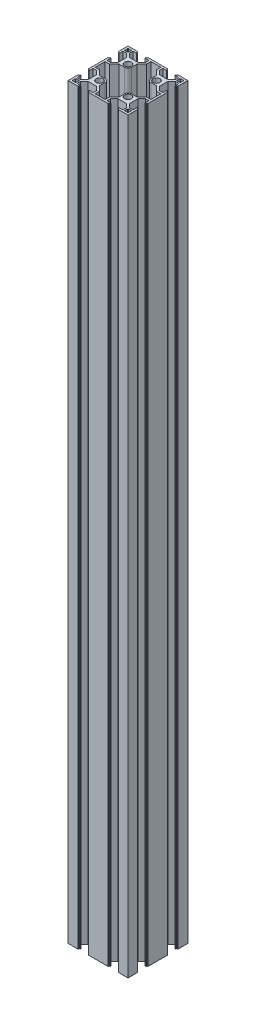
SolidWorks part; units mm, degrees
ref_plane "Front Plane" through (0, 0, 0) normal (0, 0, 1) x (1, 0, 0)
ref_plane "Top Plane" through (0, 0, 0) normal (0, 1, 0) x (1, 0, 0)
ref_plane "Right Plane" through (0, 0, 0) normal (1, 0, 0) x (0, 0, -1)
sketch "Sketch1" plane through (0, 0, 0) normal (0, 1, 0) x (1, 0, 0)
  line L0 (0, 30) -> (0, -30) construction
  line L1 (-30, -30) -> (30, -30)
  line L2 (-30, -30) -> (-30, 30)
  line L3 (-30, 30) -> (30, 30)
  line L4 (30, -30) -> (30, 30)
  line L5 (-30, -30) -> (30, 30) construction
  line L6 (-30, 30) -> (30, -30) construction
  line L7 (-30, 0) -> (30, 0) construction
  line L8 (-23.05, -28) -> (-6.95, -28)
  line L9 (-6.95, -28) -> (-6.95, -24.4)
  line L10 (-6.95, -24.4) -> (-10.615, -20.8)
  line L11 (-10.615, -20.8) -> (-19.385, -20.8)
  line L12 (-19.385, -20.8) -> (-23.05, -24.4)
  line L13 (-23.05, -24.4) -> (-23.05, -28)
  line L14 (10.615, -20.8) -> (19.385, -20.8)
  line L15 (6.95, -24.4) -> (10.615, -20.8)
  line L16 (6.95, -28) -> (6.95, -24.4)
  line L17 (23.05, -28) -> (6.95, -28)
  line L18 (23.05, -24.4) -> (23.05, -28)
  line L19 (19.385, -20.8) -> (23.05, -24.4)
  line L20 (19.385, 20.8) -> (23.05, 24.4)
  line L21 (23.05, 24.4) -> (23.05, 28)
  line L22 (23.05, 28) -> (6.95, 28)
  line L23 (6.95, 28) -> (6.95, 24.4)
  line L24 (6.95, 24.4) -> (10.615, 20.8)
  line L25 (10.615, 20.8) -> (19.385, 20.8)
  line L26 (-23.05, 24.4) -> (-23.05, 28)
  line L27 (-19.385, 20.8) -> (-23.05, 24.4)
  line L28 (-10.615, 20.8) -> (-19.385, 20.8)
  line L29 (-6.95, 24.4) -> (-10.615, 20.8)
  line L30 (-6.95, 28) -> (-6.95, 24.4)
  line L31 (-23.05, 28) -> (-6.95, 28)
  line L32 (-20.8, 19.385) -> (-24.4, 23.05)
  line L33 (-24.4, 23.05) -> (-28, 23.05)
  line L34 (-28, 23.05) -> (-28, 6.95)
  line L35 (-28, 6.95) -> (-24.4, 6.95)
  line L36 (-24.4, 6.95) -> (-20.8, 10.615)
  line L37 (-20.8, 10.615) -> (-20.8, 19.385)
  line L38 (-24.4, -23.05) -> (-28, -23.05)
  line L39 (-20.8, -19.385) -> (-24.4, -23.05)
  line L40 (-20.8, -10.615) -> (-20.8, -19.385)
  line L41 (-24.4, -6.95) -> (-20.8, -10.615)
  line L42 (-28, -6.95) -> (-24.4, -6.95)
  line L43 (-28, -23.05) -> (-28, -6.95)
  line L44 (20.8, -19.385) -> (24.4, -23.05)
  line L45 (24.4, -23.05) -> (28, -23.05)
  line L46 (28, -23.05) -> (28, -6.95)
  line L47 (28, -6.95) -> (24.4, -6.95)
  line L48 (24.4, -6.95) -> (20.8, -10.615)
  line L49 (20.8, -10.615) -> (20.8, -19.385)
  line L50 (24.4, 23.05) -> (28, 23.05)
  line L51 (20.8, 19.385) -> (24.4, 23.05)
  line L52 (20.8, 10.615) -> (20.8, 19.385)
  line L53 (24.4, 6.95) -> (20.8, 10.615)
  line L54 (28, 6.95) -> (24.4, 6.95)
  line L55 (28, 23.05) -> (28, 6.95)
  point P0 (0, 0)
  dimension "D1" = 60
  dimension "D2" = 16.1
  dimension "D3" = 8.77
  dimension "D4" = 3.6
  dimension "D5" = 7.2
  dimension "D6" = 2
  dimension "D7" = 6.95
extrude "Boss-Extrude1" add sketch "Sketch1" along normal blind 750
sketch "Sketch2" plane through (0, 750, 0) normal (0, 1, 0) x (1, 0, 0)
  line L0 (-19.1, -28) -> (-19.1, -29)
  line L1 (-23.05, -28) -> (-6.95, -28) construction
  line L2 (-30, -30) -> (30, -30) construction
  line L3 (-10.9, -28) -> (-10.9, -29)
  line L4 (-10.9, -29) -> (-9.9, -29)
  line L5 (-9.9, -29) -> (-9.9, -30)
  line L6 (-19.1, -29) -> (-20.1, -29)
  line L7 (-20.1, -29) -> (-20.1, -30)
  line L8 (-19.1, -28) -> (-10.9, -28)
  line L9 (-20.1, -30) -> (-9.9, -30)
  dimension "D1" = 8.2
  dimension "D2" = 3.95
  dimension "D3" = 1
  dimension "D4" = 1
extrude "Cut-Extrude1" cut sketch "Sketch2" against normal through all
mirror "Mirror1" about plane through (0, 0, 0) normal (1, 0, 0) of "Cut-Extrude1"
ref_axis "Axis1" through (0, 1050, 0) along (0, -1, 0)
pattern_circular "CirPattern1" count 4 over 360 about axis through (0, 1050, 0) along (0, -1, 0) of "Cut-Extrude1", "Mirror1"
sketch "Sketch4" plane through (0, 750, 0) normal (0, 1, 0) x (1, 0, 0)
  line L0 (19.385, 18.8) -> (9.797, 18.8) construction
  line L1 (-18.8, 18.8) -> (-18.8, 9.797)
  line L2 (18.8, -19.385) -> (18.8, -9.797) construction
  line L3 (28, 4.95) -> (28, -4.95)
  line L4 (-18.8, -9.797) -> (-18.8, -19.385) construction
  line L5 (4.95, -28) -> (-4.95, -28)
  line L6 (-9.797, 18.8) -> (-9.797, 13.197)
  line L7 (-28, -4.95) -> (-28, 4.95)
  line L8 (-18.8, 9.797) -> (-23.5611, 4.95)
  line L9 (-23.5611, 4.95) -> (-28, 4.95)
  line L10 (18.8, 18.8) -> (9.797, 18.8)
  line L11 (9.797, 18.8) -> (4.95, 23.5611)
  line L12 (4.95, 23.5611) -> (4.95, 28)
  line L13 (4.95, 28) -> (4.95, 28)
  line L14 (4.95, 28) -> (4.95, 28)
  line L15 (4.95, 28) -> (4.95, 28)
  line L16 (4.95, 28) -> (4.95, 28)
  line L17 (4.95, 28) -> (-4.95, 28)
  line L18 (-4.95, 28) -> (-4.95, 28)
  line L19 (-4.95, 28) -> (-4.95, 28)
  line L20 (-4.95, 28) -> (-4.95, 28)
  line L21 (-4.95, 28) -> (-4.95, 28)
  line L22 (-4.95, 28) -> (-4.95, 23.5611)
  line L23 (-4.95, 23.5611) -> (-9.797, 18.8)
  line L24 (-9.797, 18.8) -> (-18.8, 18.8)
  line L25 (28, 4.95) -> (23.5611, 4.95)
  line L26 (23.5611, 4.95) -> (18.8, 9.797)
  line L27 (18.8, 9.797) -> (18.8, 18.8)
  line L28 (18.8, -18.8) -> (18.8, -9.797)
  line L29 (18.8, -9.797) -> (23.5611, -4.95)
  line L30 (23.5611, -4.95) -> (28, -4.95)
  line L31 (4.95, -28) -> (4.95, -23.5611)
  line L32 (4.95, -23.5611) -> (9.797, -18.8)
  line L33 (9.797, -18.8) -> (18.8, -18.8)
  line L34 (-18.8, -18.8) -> (-9.797, -18.8)
  line L35 (-9.797, -18.8) -> (-4.95, -23.5611)
  line L36 (-4.95, -23.5611) -> (-4.95, -28)
  line L37 (-28, -4.95) -> (-23.5611, -4.95)
  line L38 (-23.5611, -4.95) -> (-18.8, -9.797)
  line L39 (-18.8, -9.797) -> (-18.8, -18.8)
  line L40 (-9.797, 18.8) -> (-19.385, 18.8) construction
  line L41 (-18.8, 19.385) -> (-18.8, 9.797) construction
  line L42 (18.8, 9.797) -> (18.8, 19.385) construction
  line L43 (9.797, -18.8) -> (19.385, -18.8) construction
  line L44 (-19.385, -18.8) -> (-9.797, -18.8) construction
  line L45 (-13.197, 9.797) -> (-18.8, 9.797)
  line L46 (9.797, 18.8) -> (9.797, 13.197)
  line L47 (13.197, 9.797) -> (18.8, 9.797)
  line L48 (-18.8, -9.797) -> (-13.197, -9.797)
  line L49 (-9.797, -13.197) -> (-9.797, -18.8)
  line L50 (9.797, -18.8) -> (9.797, -13.197)
  line L51 (13.197, -9.797) -> (18.8, -9.797)
  line L52 (-27.5, -28) -> (-24.9, -28)
  line L53 (24.9, -28) -> (27.5, -28)
  line L54 (24.4, -27.5) -> (24.4, -24.9)
  line L55 (24.9, -24.4) -> (27.5, -24.4)
  line L56 (28, -27.5) -> (28, -24.9)
  line L57 (24.4, -28) -> (28, -24.4) construction
  line L58 (24.4, -24.4) -> (28, -28) construction
  line L59 (-28, -24.9) -> (-28, -27.5)
  line L60 (-27.5, -24.4) -> (-24.9, -24.4)
  line L61 (-24.4, -24.9) -> (-24.4, -27.5)
  line L62 (-28, 27.5) -> (-28, 24.9)
  line L63 (-24.9, 28) -> (-27.5, 28)
  line L64 (-24.4, 27.5) -> (-24.4, 24.9)
  line L65 (-24.9, 24.4) -> (-27.5, 24.4)
  line L66 (27.5, 28) -> (24.9, 28)
  line L67 (28, 24.9) -> (28, 27.5)
  line L68 (27.5, 24.4) -> (24.9, 24.4)
  line L69 (24.4, 24.9) -> (24.4, 27.5)
  line L116 (28, 19.1) -> (29, 19.1)
  line L117 (29, 19.1) -> (29, 20.1)
  line L118 (29, 20.1) -> (30, 20.1)
  line L119 (30, 20.1) -> (30, 30)
  line L120 (30, 30) -> (20.1, 30)
  line L121 (20.1, 30) -> (20.1, 29)
  line L122 (20.1, 29) -> (19.1, 29)
  line L123 (19.1, 29) -> (19.1, 28)
  line L124 (19.1, 28) -> (23.05, 28)
  line L125 (23.05, 28) -> (23.05, 24.4)
  line L126 (23.05, 24.4) -> (19.385, 20.8)
  line L127 (19.385, 20.8) -> (10.615, 20.8)
  line L128 (10.615, 20.8) -> (6.95, 24.4)
  line L129 (6.95, 24.4) -> (6.95, 28)
  line L130 (6.95, 28) -> (10.9, 28)
  line L131 (10.9, 28) -> (10.9, 29)
  line L132 (10.9, 29) -> (9.9, 29)
  line L133 (9.9, 29) -> (9.9, 30)
  line L134 (9.9, 30) -> (-9.9, 30)
  line L135 (-9.9, 30) -> (-9.9, 29)
  line L136 (-9.9, 29) -> (-10.9, 29)
  line L137 (-10.9, 29) -> (-10.9, 28)
  line L138 (-10.9, 28) -> (-6.95, 28)
  line L139 (-6.95, 28) -> (-6.95, 24.4)
  line L140 (-6.95, 24.4) -> (-10.615, 20.8)
  line L141 (-10.615, 20.8) -> (-19.385, 20.8)
  line L142 (-19.385, 20.8) -> (-23.05, 24.4)
  line L143 (-23.05, 24.4) -> (-23.05, 28)
  line L144 (-23.05, 28) -> (-19.1, 28)
  line L145 (-19.1, 28) -> (-19.1, 29)
  line L146 (-19.1, 29) -> (-20.1, 29)
  line L147 (-20.1, 29) -> (-20.1, 30)
  line L148 (-20.1, 30) -> (-30, 30)
  line L149 (-30, 30) -> (-30, 20.1)
  line L150 (-30, 20.1) -> (-29, 20.1)
  line L151 (-29, 20.1) -> (-29, 19.1)
  line L152 (-29, 19.1) -> (-28, 19.1)
  line L153 (-28, 19.1) -> (-28, 23.05)
  line L154 (-28, 23.05) -> (-24.4, 23.05)
  line L155 (-24.4, 23.05) -> (-20.8, 19.385)
  line L156 (-20.8, 19.385) -> (-20.8, 10.615)
  line L157 (-20.8, 10.615) -> (-24.4, 6.95)
  line L158 (-24.4, 6.95) -> (-28, 6.95)
  line L159 (-28, 6.95) -> (-28, 10.9)
  line L160 (-28, 10.9) -> (-29, 10.9)
  line L161 (-29, 10.9) -> (-29, 9.9)
  line L162 (-29, 9.9) -> (-30, 9.9)
  line L163 (-30, 9.9) -> (-30, -9.9)
  line L164 (-30, -9.9) -> (-29, -9.9)
  line L165 (-29, -9.9) -> (-29, -10.9)
  line L166 (-29, -10.9) -> (-28, -10.9)
  line L167 (-28, -10.9) -> (-28, -6.95)
  line L168 (-28, -6.95) -> (-24.4, -6.95)
  line L169 (-24.4, -6.95) -> (-20.8, -10.615)
  line L170 (-20.8, -10.615) -> (-20.8, -19.385)
  line L171 (-20.8, -19.385) -> (-24.4, -23.05)
  line L172 (-24.4, -23.05) -> (-28, -23.05)
  line L173 (-28, -23.05) -> (-28, -19.1)
  line L174 (-28, -19.1) -> (-29, -19.1)
  line L175 (-29, -19.1) -> (-29, -20.1)
  line L176 (-29, -20.1) -> (-30, -20.1)
  line L177 (-30, -20.1) -> (-30, -30)
  line L178 (-30, -30) -> (-20.1, -30)
  line L179 (-20.1, -30) -> (-20.1, -29)
  line L180 (-20.1, -29) -> (-19.1, -29)
  line L181 (-19.1, -29) -> (-19.1, -28)
  line L182 (-19.1, -28) -> (-23.05, -28)
  line L183 (-23.05, -28) -> (-23.05, -24.4)
  line L184 (-23.05, -24.4) -> (-19.385, -20.8)
  line L185 (-19.385, -20.8) -> (-10.615, -20.8)
  line L186 (-10.615, -20.8) -> (-6.95, -24.4)
  line L187 (-6.95, -24.4) -> (-6.95, -28)
  line L188 (-6.95, -28) -> (-10.9, -28)
  line L189 (-10.9, -28) -> (-10.9, -29)
  line L190 (-10.9, -29) -> (-9.9, -29)
  line L191 (-9.9, -29) -> (-9.9, -30)
  line L192 (-9.9, -30) -> (9.9, -30)
  line L193 (9.9, -30) -> (9.9, -29)
  line L194 (9.9, -29) -> (10.9, -29)
  line L195 (10.9, -29) -> (10.9, -28)
  line L196 (10.9, -28) -> (6.95, -28)
  line L197 (6.95, -28) -> (6.95, -24.4)
  line L198 (6.95, -24.4) -> (10.615, -20.8)
  line L199 (10.615, -20.8) -> (19.385, -20.8)
  line L200 (19.385, -20.8) -> (23.05, -24.4)
  line L201 (23.05, -24.4) -> (23.05, -28)
  line L202 (23.05, -28) -> (19.1, -28)
  line L203 (19.1, -28) -> (19.1, -29)
  line L204 (19.1, -29) -> (20.1, -29)
  line L205 (20.1, -29) -> (20.1, -30)
  line L206 (20.1, -30) -> (30, -30)
  line L207 (30, -30) -> (30, -20.1)
  line L208 (30, -20.1) -> (29, -20.1)
  line L209 (29, -20.1) -> (29, -19.1)
  line L210 (29, -19.1) -> (28, -19.1)
  line L211 (28, -19.1) -> (28, -23.05)
  line L212 (28, -23.05) -> (24.4, -23.05)
  line L213 (24.4, -23.05) -> (20.8, -19.385)
  line L214 (20.8, -19.385) -> (20.8, -10.615)
  line L215 (20.8, -10.615) -> (24.4, -6.95)
  line L216 (24.4, -6.95) -> (28, -6.95)
  line L217 (28, -6.95) -> (28, -10.9)
  line L218 (28, -10.9) -> (29, -10.9)
  line L219 (29, -10.9) -> (29, -9.9)
  line L220 (29, -9.9) -> (30, -9.9)
  line L221 (30, -9.9) -> (30, 9.9)
  line L222 (30, 9.9) -> (29, 9.9)
  line L223 (29, 9.9) -> (29, 10.9)
  line L224 (29, 10.9) -> (28, 10.9)
  line L225 (28, 10.9) -> (28, 6.95)
  line L226 (28, 6.95) -> (24.4, 6.95)
  line L227 (24.4, 6.95) -> (20.8, 10.615)
  line L228 (20.8, 10.615) -> (20.8, 19.385)
  line L229 (20.8, 19.385) -> (24.4, 23.05)
  line L230 (24.4, 23.05) -> (28, 23.05)
  line L231 (28, 23.05) -> (28, 19.1)
  line L232 (28, 19.1) -> (29, 19.1)
  line L233 (29, 19.1) -> (29, 20.1)
  line L234 (29, 20.1) -> (30, 20.1)
  line L235 (30, 20.1) -> (30, 30)
  line L236 (30, 30) -> (20.1, 30)
  line L237 (20.1, 30) -> (20.1, 29)
  line L238 (20.1, 29) -> (19.1, 29)
  line L239 (19.1, 29) -> (19.1, 28)
  line L240 (19.1, 28) -> (23.05, 28)
  line L241 (23.05, 28) -> (23.05, 24.4)
  line L242 (23.05, 24.4) -> (19.385, 20.8)
  line L243 (19.385, 20.8) -> (10.615, 20.8)
  line L244 (10.615, 20.8) -> (6.95, 24.4)
  line L245 (6.95, 24.4) -> (6.95, 28)
  line L246 (6.95, 28) -> (10.9, 28)
  line L247 (10.9, 28) -> (10.9, 29)
  line L248 (10.9, 29) -> (9.9, 29)
  line L249 (9.9, 29) -> (9.9, 30)
  line L250 (9.9, 30) -> (-9.9, 30)
  line L251 (-9.9, 30) -> (-9.9, 29)
  line L252 (-9.9, 29) -> (-10.9, 29)
  line L253 (-10.9, 29) -> (-10.9, 28)
  line L254 (-10.9, 28) -> (-6.95, 28)
  line L255 (-6.95, 28) -> (-6.95, 24.4)
  line L256 (-6.95, 24.4) -> (-10.615, 20.8)
  line L257 (-10.615, 20.8) -> (-19.385, 20.8)
  line L258 (-19.385, 20.8) -> (-23.05, 24.4)
  line L259 (-23.05, 24.4) -> (-23.05, 28)
  line L260 (-23.05, 28) -> (-19.1, 28)
  line L261 (-19.1, 28) -> (-19.1, 29)
  line L262 (-19.1, 29) -> (-20.1, 29)
  line L263 (-20.1, 29) -> (-20.1, 30)
  line L264 (-20.1, 30) -> (-30, 30)
  line L265 (-30, 30) -> (-30, 20.1)
  line L266 (-30, 20.1) -> (-29, 20.1)
  line L267 (-29, 20.1) -> (-29, 19.1)
  line L268 (-29, 19.1) -> (-28, 19.1)
  line L269 (-28, 19.1) -> (-28, 23.05)
  line L270 (-28, 23.05) -> (-24.4, 23.05)
  line L271 (-24.4, 23.05) -> (-20.8, 19.385)
  line L272 (-20.8, 19.385) -> (-20.8, 10.615)
  line L273 (-20.8, 10.615) -> (-24.4, 6.95)
  line L274 (-24.4, 6.95) -> (-28, 6.95)
  line L275 (-28, 6.95) -> (-28, 10.9)
  line L276 (-28, 10.9) -> (-29, 10.9)
  line L277 (-29, 10.9) -> (-29, 9.9)
  line L278 (-29, 9.9) -> (-30, 9.9)
  line L279 (-30, 9.9) -> (-30, -9.9)
  line L280 (-30, -9.9) -> (-29, -9.9)
  line L281 (-29, -9.9) -> (-29, -10.9)
  line L282 (-29, -10.9) -> (-28, -10.9)
  line L283 (-28, -10.9) -> (-28, -6.95)
  line L284 (-28, -6.95) -> (-24.4, -6.95)
  line L285 (-24.4, -6.95) -> (-20.8, -10.615)
  line L286 (-20.8, -10.615) -> (-20.8, -19.385)
  line L287 (-20.8, -19.385) -> (-24.4, -23.05)
  line L288 (-24.4, -23.05) -> (-28, -23.05)
  line L289 (-28, -23.05) -> (-28, -19.1)
  line L290 (-28, -19.1) -> (-29, -19.1)
  line L291 (-29, -19.1) -> (-29, -20.1)
  line L292 (-29, -20.1) -> (-30, -20.1)
  line L293 (-30, -20.1) -> (-30, -30)
  line L294 (-30, -30) -> (-20.1, -30)
  line L295 (-20.1, -30) -> (-20.1, -29)
  line L296 (-20.1, -29) -> (-19.1, -29)
  line L297 (-19.1, -29) -> (-19.1, -28)
  line L298 (-19.1, -28) -> (-23.05, -28)
  line L299 (-23.05, -28) -> (-23.05, -24.4)
  line L300 (-23.05, -24.4) -> (-19.385, -20.8)
  line L301 (-19.385, -20.8) -> (-10.615, -20.8)
  line L302 (-10.615, -20.8) -> (-6.95, -24.4)
  line L303 (-6.95, -24.4) -> (-6.95, -28)
  line L304 (-6.95, -28) -> (-10.9, -28)
  line L305 (-10.9, -28) -> (-10.9, -29)
  line L306 (-10.9, -29) -> (-9.9, -29)
  line L307 (-9.9, -29) -> (-9.9, -30)
  line L308 (-9.9, -30) -> (9.9, -30)
  line L309 (9.9, -30) -> (9.9, -29)
  line L310 (9.9, -29) -> (10.9, -29)
  line L311 (10.9, -29) -> (10.9, -28)
  line L312 (10.9, -28) -> (6.95, -28)
  line L313 (6.95, -28) -> (6.95, -24.4)
  line L314 (6.95, -24.4) -> (10.615, -20.8)
  line L315 (10.615, -20.8) -> (19.385, -20.8)
  line L316 (19.385, -20.8) -> (23.05, -24.4)
  line L317 (23.05, -24.4) -> (23.05, -28)
  line L318 (23.05, -28) -> (19.1, -28)
  line L319 (19.1, -28) -> (19.1, -29)
  line L320 (19.1, -29) -> (20.1, -29)
  line L321 (20.1, -29) -> (20.1, -30)
  line L322 (20.1, -30) -> (30, -30)
  line L323 (30, -30) -> (30, -20.1)
  line L324 (30, -20.1) -> (29, -20.1)
  line L325 (29, -20.1) -> (29, -19.1)
  line L326 (29, -19.1) -> (28, -19.1)
  line L327 (28, -19.1) -> (28, -23.05)
  line L328 (28, -23.05) -> (24.4, -23.05)
  line L329 (24.4, -23.05) -> (20.8, -19.385)
  line L330 (20.8, -19.385) -> (20.8, -10.615)
  line L331 (20.8, -10.615) -> (24.4, -6.95)
  line L332 (24.4, -6.95) -> (28, -6.95)
  line L333 (28, -6.95) -> (28, -10.9)
  line L334 (28, -10.9) -> (29, -10.9)
  line L335 (29, -10.9) -> (29, -9.9)
  line L336 (29, -9.9) -> (30, -9.9)
  line L337 (30, -9.9) -> (30, 9.9)
  line L338 (30, 9.9) -> (29, 9.9)
  line L339 (29, 9.9) -> (29, 10.9)
  line L340 (29, 10.9) -> (28, 10.9)
  line L341 (28, 10.9) -> (28, 6.95)
  line L342 (28, 6.95) -> (24.4, 6.95)
  line L343 (24.4, 6.95) -> (20.8, 10.615)
  line L344 (20.8, 10.615) -> (20.8, 19.385)
  line L345 (20.8, 19.385) -> (24.4, 23.05)
  line L346 (24.4, 23.05) -> (28, 23.05)
  line L347 (28, 23.05) -> (28, 19.1)
  circle A0 centre (14.2985, 14.2985) radius 3.4
  arc A1 (13.197, -9.797) -> (9.797, -13.197) centre (13.197, -13.197) ccw
  arc A2 (-9.797, -13.197) -> (-13.197, -9.797) centre (-13.197, -13.197) ccw
  arc A3 (13.197, 9.797) -> (9.797, 13.197) centre (13.197, 13.197) cw
  arc A4 (-9.797, 13.197) -> (-13.197, 9.797) centre (-13.197, 13.197) cw
  circle A5 centre (14.2985, -14.2985) radius 3.4
  circle A6 centre (-14.2985, -14.2985) radius 3.4
  circle A7 centre (-14.2985, 14.2985) radius 3.4
  arc A8 (24.4, -27.5) -> (24.9, -28) centre (24.9, -27.5) ccw
  arc A9 (28, -27.5) -> (27.5, -28) centre (27.5, -27.5) cw
  arc A10 (28, -24.9) -> (27.5, -24.4) centre (27.5, -24.9) ccw
  arc A11 (24.4, -24.9) -> (24.9, -24.4) centre (24.9, -24.9) cw
  arc A12 (-27.5, -28) -> (-28, -27.5) centre (-27.5, -27.5) cw
  arc A13 (-27.5, -24.4) -> (-28, -24.9) centre (-27.5, -24.9) ccw
  arc A14 (-24.9, -24.4) -> (-24.4, -24.9) centre (-24.9, -24.9) cw
  arc A15 (-24.9, -28) -> (-24.4, -27.5) centre (-24.9, -27.5) ccw
  arc A16 (-28, 27.5) -> (-27.5, 28) centre (-27.5, 27.5) cw
  arc A17 (-24.4, 27.5) -> (-24.9, 28) centre (-24.9, 27.5) ccw
  arc A18 (-24.4, 24.9) -> (-24.9, 24.4) centre (-24.9, 24.9) cw
  arc A19 (-28, 24.9) -> (-27.5, 24.4) centre (-27.5, 24.9) ccw
  arc A20 (27.5, 28) -> (28, 27.5) centre (27.5, 27.5) cw
  arc A21 (27.5, 24.4) -> (28, 24.9) centre (27.5, 24.9) ccw
  arc A22 (24.9, 24.4) -> (24.4, 24.9) centre (24.9, 24.9) cw
  arc A23 (24.9, 28) -> (24.4, 27.5) centre (24.9, 27.5) ccw
  point P102 (26.2, -26.2)
  point P104 (14.2985, 18.8)
  point P106 (18.8, 14.2985)
  point P140 (0, 0)
  point P239 (0, 0)
  dimension "D3" = 6.8
  dimension "D4" = 3.4
  dimension "D6" = 0.5
  dimension "D1" = 0
  dimension "D2" = 2
  dimension "D5" = 4
  dimension "D7" = 4
extrude "Cut-Extrude2" cut sketch "Sketch4" against normal through all contours L6 A4 L45 L8 L9 L7 L37 L38 L48 A2 L49 L35 L36 L5 L31 L32 L50 A1 L51 L29 L30 L3 L25 L26 L47 A3 L46 L11 L12 L17 L22 L23 | A7 | A0 | L66 A23 L69 A22 L68 A21 L67 A20 | L62 A19 L65 A18 L64 A17 L63 A16 | L52 A15 L61 A14 L60 A13 L59 A12 | A11 L54 A8 L53 A9 L56 A10 L55 | A6 | A5 region at (0, 750, 0) region at (-26.2, 750, 26.2) region at (26.2, 750, 26.2) region at (-26.2, 750, -26.2) region at (26.2, 750, -26.2) region at (14.2985, 750, -14.2985) region at (-14.2985, 750, -14.2985)
fillet "Fillet1" radius 0.2 16 edges at (28, 375, -19.1) (30, 375, -20.1) (29, 375, -20.1) (29, 375, -19.1) (28, 375, 10.9) (29, 375, 9.9) (28, 375, 19.1) (29, 375, 20.1) (30, 375, 20.1) (29, 375, 19.1) (29, 375, 10.9) (30, 375, 9.9) (30, 375, -9.9) (29, 375, -9.9) (29, 375, -10.9) (28, 375, -10.9)
fillet "Fillet2" radius 0.2 20 edges at (-20.1, 0, -29.5) (-20.1, 750, -29.5) (-20.1, 375, -29) (-19.6, 0, -29) (-19.1, 375, -29) (-19.6, 750, -29) (-9.9, 375, -30) (-10.9, 375, -28) (-10.9, 375, -29) (-9.9, 375, -29) (19.1, 375, -28) (19.1, 375, -29) (20.1, 375, -29) (20.1, 375, -30) (10.9, 375, -28) (10.9, 375, -29) (9.9, 375, -29) (9.9, 375, -30) (-19.1, 375, -28) (-20.1, 375, -30)
fillet "Fillet3" radius 0.2 14 edges at (-29, 375, 9.9) (-29, 375, -20.1) (-30, 375, -20.1) (-29, 375, -19.1) (-28, 375, -10.9) (-29, 375, -10.9) (-29, 375, -9.9) (-30, 375, -9.9) (-29, 375, 10.9) (-30, 375, 9.9) (-28, 375, 19.1) (-29, 375, 19.1) (-29, 375, 20.1) (-30, 375, 20.1)
fillet "Fillet4" radius 0.2 16 edges at (-19.1, 375, 28) (10.9, 375, 28) (19.1, 375, 28) (20.1, 375, 29) (-10.9, 375, 28) (-9.9, 375, 29) (9.9, 375, 29) (-20.1, 375, 29) (19.1, 375, 29) (20.1, 375, 30) (10.9, 375, 29) (9.9, 375, 30) (-9.9, 375, 30) (-10.9, 375, 29) (-19.1, 375, 29) (-20.1, 375, 30)
